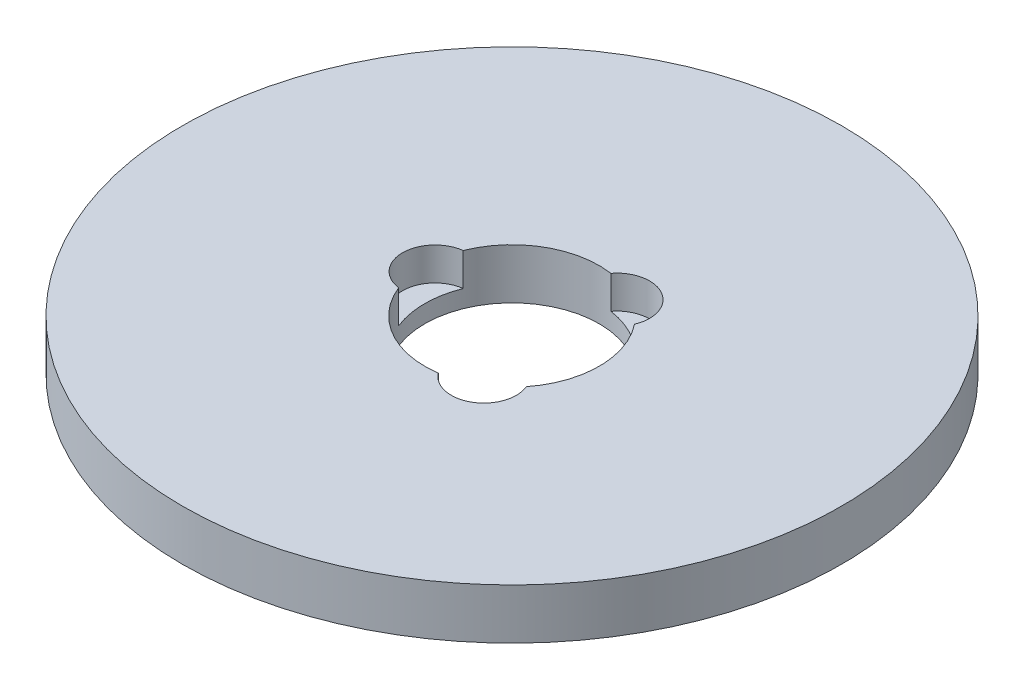
SolidWorks part; units mm, degrees
ref_plane "Front Plane" through (0, 0, 0) normal (0, 0, 1) x (1, 0, 0)
ref_plane "Top Plane" through (0, 0, 0) normal (0, 1, 0) x (1, 0, 0)
ref_plane "Right Plane" through (0, 0, 0) normal (1, 0, 0) x (0, 0, -1)
sketch "Sketch1" plane through (0, 0, 0) normal (0, 1, 0) x (1, 0, 0)
  circle A0 centre (0, 0) radius 85
  dimension "FLANGE_OD" = 170
extrude "Boss-Extrude1" add sketch "Sketch1" along normal blind 13
sketch "Sketch2" plane through (0, 0, 0) normal (0, 1, 0) x (1, 0, 0)
  circle A0 centre (0, 0) radius 22.5
  dimension "BORE_D" = 45
extrude "Cut-Extrude1" cut sketch "Sketch2" along normal through all
sketch "Sketch3" plane through (0, 13, 0) normal (0, 1, 0) x (1, 0, 0)
  circle A0 centre (0, 0) radius 19.8394 construction
  circle A1 centre (-19.8394, 0) radius 8.3869
  dimension "BOLT_D" = 16.7738
  dimension "BOLT_PCD" = 39.6788
extrude "Cut-Extrude2" cut sketch "Sketch3" against normal blind 8.4895
pattern_circular "CirPattern1" count 3 over 360 about axis through (0, 0, 0) along (0, 1, 0) of "Cut-Extrude2"
